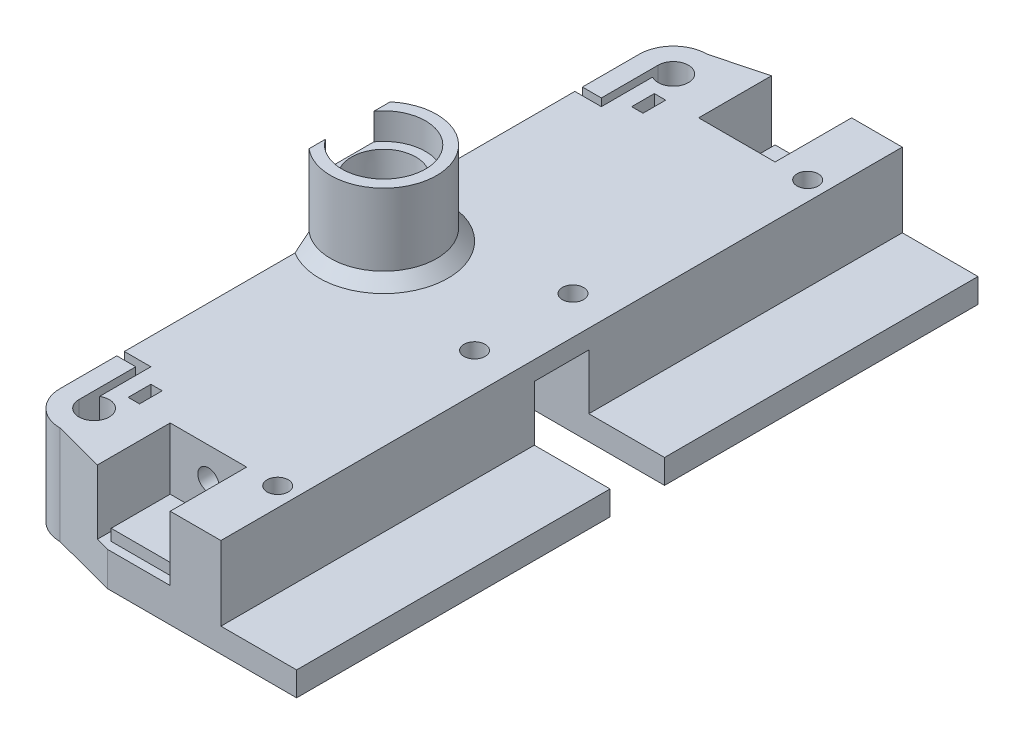
SolidWorks part; units mm, degrees
ref_plane "Płaszczyzna przednia" through (0, 0, 0) normal (0, 0, 1) x (1, 0, 0)
ref_plane "Płaszczyzna górna" through (0, 0, 0) normal (0, 1, 0) x (1, 0, 0)
ref_plane "Płaszczyzna prawa" through (0, 0, 0) normal (1, 0, 0) x (0, 0, -1)
sketch "Szkic1" plane through (0, 0, 0) normal (0, 0, 1) x (1, 0, 0)
  line L0 (10, -10) -> (10, -16)
  line L1 (10, -10) -> (-10, -10)
  line L2 (10, -10) -> (10, 10)
  line L3 (10, 10) -> (-10, 10)
  line L4 (-10, -10) -> (-10, 10)
  line L5 (10, -10) -> (-10, 10) construction
  line L6 (10, 10) -> (-10, -10) construction
  line L7 (10, -16) -> (-40, -16)
  line L8 (-40, -16) -> (-40, 10)
  line L9 (-40, 10) -> (-10, 10)
  point P0 (0, 0)
  dimension "D1" = 20
  dimension "D2" = 50
  dimension "D4" = 6
extrude "Dodanie-wyciągnięcie1" add sketch "Szkic1" along normal blind 180 contours L8 L7 L0 L1 L4 L3 region at (-21.6667, -4.3333, 0)
sketch "Szkic2" plane through (0, 10, 0) normal (0, 1, 0) x (1, 0, 0)
  line L0 (-10, -180) -> (-10, 0) construction
  line L3 (-40, -180) -> (-40, 0) construction
  line L4 (-40, 0) -> (-57, -4.5)
  line L5 (-40, -180) -> (-57, -175.5)
  line L6 (-66, -166.5) -> (-66, -13.5)
  line L7 (-40, 0) -> (-40, -180)
  circle A0 centre (-57, -13.5) radius 4
  circle A1 centre (-57, -166.5) radius 4
  circle A2 centre (-57, -13.5) radius 9
  circle A3 centre (-57, -166.5) radius 9
  circle A4 centre (-57, -90) radius 4
  point P14 (-40, -90)
  line M2 (-40, 0) -> (-40, -180)
  dimension "D1" = 47
  dimension "D2" = 8
  dimension "D6" = 8
  dimension "D3" = 153
  dimension "D4" = 76.5
  dimension "D5" = 5
extrude "Dodanie-wyciągnięcie2" add sketch "Szkic2" against normal blind 26 contours A2 A0 | A3 L5 L4 A2 L6 M2 | A3 A1 region at (-52.1906, 10, 90) region at (-50.816, 10, 7.316) region at (-63.184, 10, 172.684)
sketch "Szkic3" plane through (0, 10, 0) normal (0, 1, 0) x (1, 0, 0)
  line L0 (-61, -13.5) -> (-61, -28.5)
  line L1 (-61, -28.5) -> (-66, -28.5)
  line L2 (-66, -166.5) -> (-66, -13.5) construction
  line L3 (-66, -30.5) -> (-59, -30.5)
  line L4 (-59, -30.5) -> (-59, -16.9641)
  line L5 (-66, -28.5) -> (-66, -30.5)
  circle A0 centre (-57, -13.5) radius 4 construction
  circle A1 centre (-57, -13.5) radius 4
  line M8 (-66, -13.5) -> (-66, -166.5)
  circle M13 centre (-57, -13.5) radius 4
  dimension "D3" = 8
  dimension "D1" = 2
  dimension "D2" = 2
  dimension "D4" = 15
extrude "Wytnij-wyciągnięcie1" cut sketch "Szkic3" against normal blind 26 contours L3 L4 L0 L1 M13 M8 region at (-60.9181, 10, 24.8168)
sketch "Szkic4" plane through (-66, 0, 0) normal (-1, 0, 0) x (0, 0, 1)
  line L0 (28.5, -16) -> (28.5, 10) construction
  line L1 (28.5, 10) -> (13.5, 10) construction
  circle A0 centre (23.5, 3) radius 1.75
  circle A1 centre (23.5, -9) radius 1.75
  dimension "D1" = 3.5
  dimension "D2" = 12
  dimension "D3" = 5
  dimension "D4" = 7
extrude "Wytnij-wyciągnięcie2" cut sketch "Szkic4" against normal blind 11
sketch "Szkic5" plane through (-66, 0, 0) normal (-1, 0, 0) x (0, 0, 1)
  line L0 (20.5, 4.7321) -> (20.5, 10)
  line L1 (23.5, 6.4641) -> (20.5, 4.7321)
  line L2 (20.5, 4.7321) -> (20.5, 1.2679)
  line L3 (20.5, 1.2679) -> (23.5, -0.4641)
  line L4 (23.5, -0.4641) -> (26.5, 1.2679)
  line L5 (26.5, 1.2679) -> (26.5, 4.7321)
  line L6 (26.5, 4.7321) -> (23.5, 6.4641)
  line L7 (23.5, -5.5359) -> (20.5, -7.2679)
  line L8 (20.5, -7.2679) -> (20.5, -10.7321)
  line L9 (20.5, -10.7321) -> (23.5, -12.4641)
  line L10 (23.5, -12.4641) -> (26.5, -10.7321)
  line L11 (26.5, -10.7321) -> (26.5, -7.2679)
  line L12 (26.5, -7.2679) -> (23.5, -5.5359)
  line L13 (28.5, 10) -> (13.5, 10) construction
  line L14 (20.5, 10) -> (26.5, 10)
  line L15 (26.5, 10) -> (26.5, 4.7321)
  line L16 (26.5, -10.7321) -> (26.5, -16)
  line L17 (28.5, -16) -> (13.5, -16) construction
  line L18 (26.5, -16) -> (20.5, -16)
  line L19 (20.5, -16) -> (20.5, -10.7321)
  circle A0 centre (23.5, 3) radius 3 construction
  circle A1 centre (23.5, -9) radius 3 construction
  circle M3 centre (23.5, 3) radius 1.75
  circle M4 centre (23.5, -9) radius 1.75
  line M5 (13.5, -16) -> (28.5, -16)
  line M7 (28.5, 10) -> (13.5, 10)
  dimension "D1" = 6
extrude "Wytnij-wyciągnięcie3" cut sketch "Szkic5" against normal blind 3 from offset 11 contours L5 L6 L1 L2 L3 L4 M3 | L15 L0 L1 L6 M7 | L11 L12 L7 L8 L9 L10 M4 | L19 L16 L10 L9 M5 | M4 | M3 region at (-66, 7.7706, 23.5) region at (-66, 5.5187, 22.0458) region at (-66, -6.4813, 24.9542) region at (-66, -13.7706, 23.5) region at (-66, 3, 23.5) region at (-66, -9, 23.5) offset against normal yes
sketch "Szkic6" plane through (0, -16, 0) normal (0, -1, 0) x (1, 0, 0)
  line L0 (-57, 9.5) -> (-57, 17.5)
  arc A0 (-61, 13.5) -> (-59, 16.9641) centre (-57, 13.5) ccw construction
  arc A1 (-61, 13.5) -> (-59, 16.9641) centre (-57, 13.5) ccw
  arc M13 (-59, 16.9641) -> (-61, 13.5) centre (-57, 13.5) cw
extrude "Dodanie-wyciągnięcie3" add sketch "Szkic6" against normal blind 2 contours L0 M13 region at (-55.3023, -16, 13.5)
ref_plane "Płaszczyzna1" through (0, 0, 90) normal (0, 0, 1) x (1, 0, 0)
mirror "Lustro1" about plane through (0, 0, 90) normal (0, 0, 1) of "Dodanie-wyciągnięcie3", "Wytnij-wyciągnięcie3", "Wytnij-wyciągnięcie2", "Wytnij-wyciągnięcie1"
sketch "Szkic7" plane through (0, -16, 0) normal (0, -1, 0) x (1, 0, 0)
  line L0 (-63, 94.2) -> (-63, 85.8)
  line L1 (-60, 97.2) -> (-55.2, 97.2)
  line L2 (-60, 82.8) -> (-55.2, 82.8)
  line L3 (-48.2, 97.2) -> (11.5715, 97.2)
  line L4 (11.5715, 97.2) -> (11.5715, 82.8)
  line L5 (11.5715, 82.8) -> (-48.2, 82.8)
  circle A0 centre (-57, 90) radius 4 construction
  circle A1 centre (-57, 90) radius 4
  arc A2 (-63, 85.8) -> (-60, 82.8) centre (-60, 85.8) ccw
  arc A3 (-63, 94.2) -> (-60, 97.2) centre (-60, 94.2) cw
  arc A5 (-48.2, 97.2) -> (-55.2, 97.2) centre (-51.7, 97.2) ccw
  arc A7 (-55.2, 82.8) -> (-48.2, 82.8) centre (-51.7, 82.8) ccw
  point P16 (-63, 90)
  circle M6 centre (-57, 90) radius 4
  dimension "D2" = 3
  dimension "D3" = 11.3
  dimension "D4" = 3.5
  dimension "D1" = 6
  dimension "D5" = 14.4
extrude "Wytnij-wyciągnięcie5" cut sketch "Szkic7" against normal blind 21 contours M6 | L2 A7 L5 L4 L3 A5 L1 A3 L0 A2 M6 region at (-25.0395, -16, 90) region at (-57, -16, 90)
sketch "Szkic8" plane through (0, 5, 0) normal (0, -1, 0) x (1, 0, 0)
  line L1 (-48.2, 94.5) -> (-35.2, 94.5)
  line L2 (-48.2, 94.5) -> (-48.2, 85.5)
  line L3 (-48.2, 85.5) -> (-35.2, 85.5)
  line L4 (-35.2, 94.5) -> (-35.2, 85.5)
  circle A0 centre (-57, 90) radius 4 construction
  circle A1 centre (-57, 90) radius 4
  arc A2 (-55.2, 82.8) -> (-48.2, 82.8) centre (-51.7, 82.8) ccw construction
  arc A3 (-48.2, 97.2) -> (-55.2, 97.2) centre (-51.7, 97.2) ccw construction
  arc A4 (-55.2, 82.8) -> (-48.2, 82.8) centre (-51.7, 82.8) ccw
  arc A5 (-48.2, 97.2) -> (-55.2, 97.2) centre (-51.7, 97.2) ccw
  circle A6 centre (-51.7, 97.2) radius 2
  circle A7 centre (-51.7, 82.8) radius 2
  point P7 (-48.2, 90)
  dimension "D4" = 4
  dimension "D1" = 9
  dimension "D2" = 13
  dimension "D3" = 8.8
extrude "Wytnij-wyciągnięcie6" cut sketch "Szkic8" against normal blind 4 contours L4 L1 L2 L3 | A6 | A7 region at (-41.7, 5, 90) region at (-51.7, 5, 97.2) region at (-51.7, 5, 82.8)
sketch "Szkic9" plane through (0, 10, 0) normal (0, 1, 0) x (1, 0, 0)
  circle A0 centre (-57, -90) radius 14
  circle A1 centre (-57, -90) radius 4 construction
  circle A2 centre (-57, -90) radius 4
extrude "Dodanie-wyciągnięcie4" add sketch "Szkic9" along normal blind 22
sketch "Szkic10" plane through (0, 32, 0) normal (0, 1, 0) x (1, 0, 0)
  circle A0 centre (-57, -90) radius 4 construction
  circle A1 centre (-57, -90) radius 4
  circle A2 centre (-57, -90) radius 11.05
  dimension "D1" = 22.1
extrude "Wytnij-wyciągnięcie7" cut sketch "Szkic10" against normal blind 7
sketch "Szkic11" plane through (0, 25, 0) normal (0, 1, 0) x (1, 0, 0)
  circle A0 centre (-57, -90) radius 8
  circle A1 centre (-57, -90) radius 11.05
  circle A2 centre (-57, -90) radius 11.05
  circle M2 centre (-57, -90) radius 4
  dimension "D2" = 16
  dimension "D1" = 0
extrude "Wytnij-wyciągnięcie8" cut sketch "Szkic11" against normal blind 15 contours A0 M2 region at (-64.7737, 25, 90)
chamfer "Sfazowanie1" distance 0.5 distance2 12 1 edges at (-57, 25, 98) first distance on face at (-57, 25, 98)
sketch "Szkic12" plane through (0, 10, 0) normal (0, 1, 0) x (1, 0, 0)
  line L1 (-66, -100.7238) -> (-66, -79.2762)
  line L2 (-66, -100.7238) -> (-66, -79.2762)
  arc A1 (-66, -79.2762) -> (-66, -100.7238) centre (-57, -90) ccw
  arc A2 (-66, -79.2762) -> (-66, -100.7238) centre (-57, -90) ccw
  dimension "D1" = 0
extrude "Wytnij-wyciągnięcie9" cut sketch "Szkic12" along normal blind 22
sketch "Szkic13" plane through (0, -16, 0) normal (0, -1, 0) x (1, 0, 0)
  line L0 (10, 82.8) -> (-48.2, 82.8) construction
  line L1 (-60, 104.2) -> (-30, 104.2)
  line L2 (-65, 99.2) -> (-65, 80.8)
  line L3 (-60, 75.8) -> (-30, 75.8)
  line L4 (-25, 99.2) -> (-25, 80.8)
  arc A0 (-65, 80.8) -> (-60, 75.8) centre (-60, 80.8) ccw
  arc A1 (-30, 75.8) -> (-25, 80.8) centre (-30, 80.8) ccw
  arc A2 (-30, 104.2) -> (-25, 99.2) centre (-30, 99.2) cw
  arc A3 (-60, 104.2) -> (-65, 99.2) centre (-60, 99.2) ccw
  circle A4 centre (-57, 90) radius 4 construction
  circle A5 centre (-57, 90) radius 4
  point P6 (-65, 75.8)
  point P11 (-25, 104.2)
  point P14 (-65, 104.2)
  point P18 (-65, 90)
  dimension "D3" = 5
  dimension "D1" = 7
  dimension "D2" = 40
  dimension "D4" = 8
extrude "Wytnij-wyciągnięcie10" cut sketch "Szkic13" against normal blind 3
sketch "Szkic14" plane through (0, -13, 0) normal (0, -1, 0) x (1, 0, 0)
  line L0 (-30, 104.2) -> (-60, 104.2) construction
  line L1 (-65, 99.2) -> (-65, 80.8) construction
  line L2 (-60, 75.8) -> (-30, 75.8) construction
  line L3 (-25, 97.2) -> (-25, 99.2) construction
  circle A0 centre (-60, 101.2) radius 2
  circle A1 centre (-30, 101.2) radius 2
  circle A2 centre (-30, 78.8) radius 2
  circle A3 centre (-60, 78.8) radius 2
  dimension "D1" = 3
  dimension "D3" = 4
  dimension "D4" = 3
  dimension "D2" = 5
  dimension "D5" = 5
extrude "Wytnij-wyciągnięcie11" cut sketch "Szkic14" against normal blind 8
sketch "Szkic15" plane through (0, 10, 0) normal (0, 1, 0) x (1, 0, 0)
  line L0 (-10, -180) -> (-10, 0) construction
  line L1 (-40, -180) -> (-10, -180) construction
  line L2 (-40, 0) -> (-10, 0) construction
  circle A0 centre (-15, -160) radius 2.8
  circle A1 centre (-20, -103) radius 2.8
  circle A2 centre (-15, -20) radius 2.8
  circle A3 centre (-20, -77) radius 2.8
  point P12 (-10, -90)
  dimension "D1" = 5.6
  dimension "D6" = 26
  dimension "D2" = 5
  dimension "D3" = 10
  dimension "D4" = 20
  dimension "D5" = 20
  dimension "D7" = 13
extrude "Wytnij-wyciągnięcie12" cut sketch "Szkic15" against normal blind 10
chamfer "Sfazowanie2" distance 3 angle 45 1 edges at (-43, 10, 90)
sketch "Szkic16" plane through (0, 10, 0) normal (0, 1, 0) x (1, 0, 0)
  line L1 (-23.4, -180) -> (-43.6, -180)
  line L2 (-23.4, -180) -> (-23.4, -159.8)
  line L3 (-23.4, -159.8) -> (-43.6, -159.8)
  line L4 (-43.6, -180) -> (-43.6, -159.8)
  line L5 (-66, -149.5) -> (-66, -104.4222) construction
  dimension "D1" = 20.2
  dimension "D2" = 20.2
  dimension "D3" = 22.4
extrude "Wytnij-wyciągnięcie13" cut sketch "Szkic16" against normal blind 17
sketch "Szkic17" plane through (0, -7, 0) normal (0, 1, 0) x (1, 0, 0)
  line L0 (-23.4, -159.8) -> (-43.6, -159.8) construction
  line L1 (-41.3, -177.7) -> (-25.7, -177.7)
  line L2 (-41.3, -177.7) -> (-41.3, -162.1)
  line L3 (-41.3, -162.1) -> (-25.7, -162.1)
  line L4 (-25.7, -177.7) -> (-25.7, -162.1)
  line L5 (-41.3, -177.7) -> (-25.7, -162.1) construction
  line L6 (-41.3, -162.1) -> (-25.7, -177.7) construction
  line L7 (-23.4, -180) -> (-23.4, -159.8) construction
  point P0 (-33.5, -169.9)
  dimension "D1" = 15.6
  dimension "D2" = 2.3
  dimension "D3" = 2.3
extrude "Dodanie-wyciągnięcie5" add sketch "Szkic17" along normal blind 3
sketch "Szkic18" plane through (0, 0, 159.8) normal (0, 0, 1) x (1, 0, 0)
  line L1 (-23.4, 10) -> (-43.6, 10) construction
  circle A0 centre (-33.5, 2) radius 2.8
  point P2 (-33.5, 10)
  dimension "D1" = 5.6
  dimension "D2" = 8
extrude "Wytnij-wyciągnięcie14" cut sketch "Szkic18" against normal blind 10
mirror "Lustro2" about plane through (0, 0, 90) normal (0, 0, 1) of "Wytnij-wyciągnięcie14", "Dodanie-wyciągnięcie5", "Wytnij-wyciągnięcie13"
sketch "Szkic19" plane through (0, -10, 0) normal (0, 1, 0) x (1, 0, 0)
  line L0 (-10, -82.8) -> (10, -82.8) construction
  line L1 (10, -82.8) -> (10, 0) construction
  line L2 (10, 0) -> (-10, 0) construction
  line L3 (-10, 0) -> (-10, -82.8) construction
  line L4 (10, -97.2) -> (-10, -97.2) construction
  line L5 (-10, -97.2) -> (-10, -180) construction
  line L6 (-10, -180) -> (10, -180) construction
  line L7 (10, -180) -> (10, -97.2) construction
  line L8 (-10, -82.8) -> (10, -82.8)
  line L9 (10, -82.8) -> (10, 0)
  line L10 (10, 0) -> (-10, 0)
  line L11 (-10, 0) -> (-10, -82.8)
  line L12 (10, -97.2) -> (-10, -97.2)
  line L13 (-10, -97.2) -> (-10, -180)
  line L14 (-10, -180) -> (10, -180)
  line L15 (10, -180) -> (10, -97.2)
extrude "Dodanie-wyciągnięcie6" add sketch "Szkic19" along normal blind 0.4
